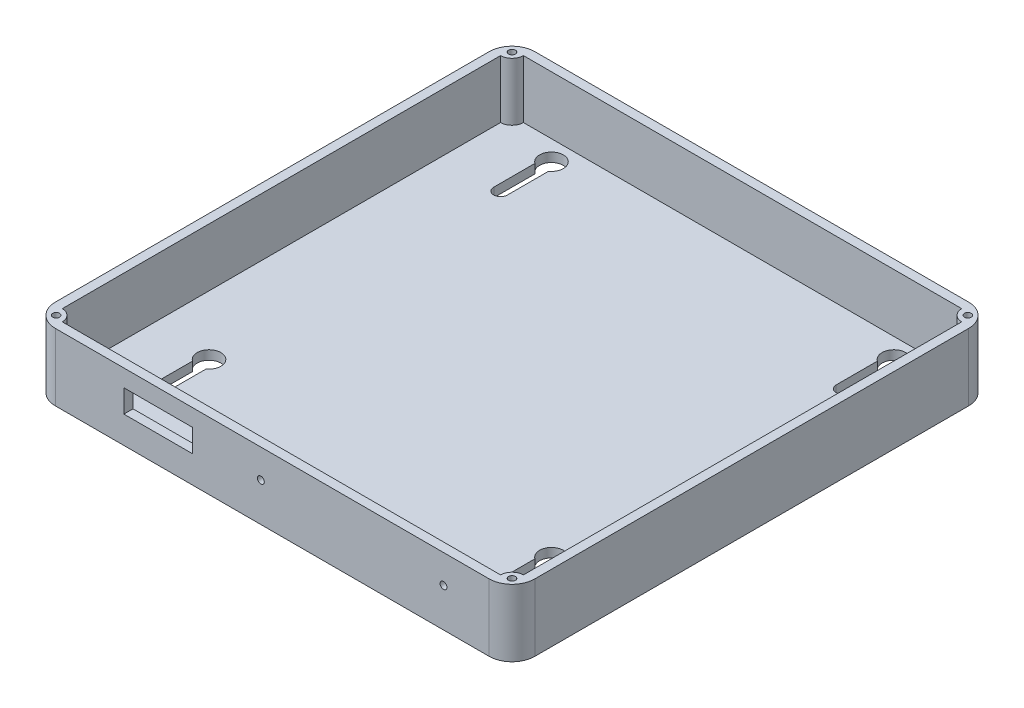
SolidWorks part; units mm, degrees
ref_plane "Front Plane" through (0, 0, 0) normal (0, 0, 1) x (1, 0, 0)
ref_plane "Top Plane" through (0, 0, 0) normal (0, 1, 0) x (1, 0, 0)
ref_plane "Right Plane" through (0, 0, 0) normal (1, 0, 0) x (0, 0, -1)
sketch "Sketch1" plane through (0, 0, 0) normal (0, 1, 0) x (1, 0, 0)
  line L0 (-101, -101) -> (-101, 101)
  line L1 (-105, -105) -> (105, -105)
  line L2 (-105, -105) -> (-105, 105)
  line L3 (-105, 105) -> (105, 105)
  line L4 (105, -105) -> (105, 105)
  line L5 (-101, 101) -> (101, 101)
  line L6 (101, -101) -> (101, 101)
  line L7 (-101, -101) -> (101, -101)
  point P0 (0, 0)
  point P6 (0, 105)
  point P7 (-105, 0)
  dimension "D1" = 210
  dimension "D2" = 210
  dimension "D3" = 4
extrude "Base" add sketch "Sketch1" along normal blind 4 contours L1 L4 L3 L2
extrude "Walls" add sketch "Sketch1<3>" along normal blind 25.4 from surface starting at face at (0, 4, 0)
sketch "Sketch1<3>" plane through (0, 0, 0) normal (0, 1, 0) x (1, 0, 0) same geometry as "Sketch1"
sketch "Sketch2" plane through (0, 29.4, 0) normal (0, 1, 0) x (1, 0, 0)
  line L0 (-101, 101) -> (-101, 96)
  line L1 (-101, 101) -> (-101, -101) construction
  line L2 (-101, 101) -> (-96, 101)
  line L3 (101, 101) -> (-101, 101) construction
  line L12 (-101, 101) -> (-97.4645, 97.4645) construction
  line L27 (-16.72, 0) -> (16.72, 0) construction
  line L28 (-101, -101) -> (-101, -96)
  line L29 (-101, -101) -> (-96, -101)
  line L30 (0, -16.72) -> (0, 16.72) construction
  line L31 (101, 101) -> (101, 96)
  line L32 (101, 101) -> (96, 101)
  line L33 (101, -101) -> (96, -101)
  line L34 (101, -101) -> (101, -96)
  arc A0 (-101, 96) -> (-96, 101) centre (-101, 101) ccw
  circle A18 centre (-99.8333, 99.8333) radius 1.5
  arc A19 (-101, -96) -> (-96, -101) centre (-101, -101) cw
  circle A20 centre (-99.8333, -99.8333) radius 1.5
  arc A21 (101, 96) -> (96, 101) centre (101, 101) cw
  circle A22 centre (99.8333, 99.8333) radius 1.5
  circle A23 centre (99.8333, -99.8333) radius 1.5
  arc A24 (101, -96) -> (96, -101) centre (101, -101) ccw
  dimension "D2" = 1.65
  dimension "D3" = 3
  dimension "D1" = 5
extrude "ScrewMounts" add sketch "Sketch2" against normal up to surface (25.4 mm away) contours A0 L2 L0 | A20 | L28 A19 L29 | L33 A24 L34 | L31 A21 L32 up to face at (0, 4, 0)
extrude "ScrewHoles" cut sketch "Sketch2<5>" against normal blind 12.5 contours A23 | A18 | A20 | A22
sketch "Sketch2<5>" plane through (0, 29.4, 0) normal (0, 1, 0) x (1, 0, 0) same geometry as "Sketch2"
fillet "RoundedCorners" radius 10 4 edges at (-105, 14.7, -105) (105, 14.7, -105) (105, 14.7, 105) (-105, 14.7, 105)
sketch "Sketch3" plane through (0, 0, 0) normal (0, -1, 0) x (1, 0, 0)
  line L0 (-77.985, 80) -> (-77.985, 61.974)
  line L1 (-72.015, 80) -> (-72.015, 61.974)
  line L2 (-105, 95) -> (-105, -95) construction
  line L3 (-95, 105) -> (95, 105) construction
  line L4 (0, -16.72) -> (0, 16.72) construction
  line L5 (77.985, 80) -> (77.985, 61.974)
  line L6 (72.015, 80) -> (72.015, 61.974)
  line L7 (-75, 57.71) -> (75, 57.71) construction
  line L8 (-75, 57.71) -> (-75, -92.29) construction
  line L9 (72.015, -70) -> (72.015, -88.026)
  line L10 (-77.985, -70) -> (-77.985, -88.026)
  line L11 (-72.015, -70) -> (-72.015, -88.026)
  line L12 (77.985, -70) -> (77.985, -88.026)
  arc A0 (-77.985, 61.974) -> (-72.015, 61.974) centre (-75, 57.71) ccw
  arc A1 (-72.015, 80) -> (-77.985, 80) centre (-75, 80) ccw
  arc A2 (72.015, 80) -> (77.985, 80) centre (75, 80) cw
  arc A3 (77.985, 61.974) -> (72.015, 61.974) centre (75, 57.71) cw
  arc A6 (-77.985, -88.026) -> (-72.015, -88.026) centre (-75, -92.29) ccw
  arc A7 (-77.985, -70) -> (-72.015, -70) centre (-75, -70) cw
  arc A8 (77.985, -70) -> (72.015, -70) centre (75, -70) ccw
  arc A9 (77.985, -88.026) -> (72.015, -88.026) centre (75, -92.29) cw
  dimension "D2" = 10.41
  dimension "D3" = 5.97
  dimension "D7" = 150
  dimension "D1" = 22.29
  dimension "D4" = 30
  dimension "D5" = 25
  dimension "D6" = 150
extrude "BackHoleMounts" cut sketch "Sketch3" against normal up to surface (4 mm away) up to face at (0, 4, 0)
sketch "Sketch4" plane through (0, 0, 105) normal (0, 0, 1) x (1, 0, 0)
  line L0 (-95, 0) -> (95, 0) construction
  line L1 (95, 0) -> (95, 29.4) construction
  line L3 (-65, 11.9) -> (-35, 11.9)
  line L4 (-65, 11.9) -> (-65, 21.9)
  line L5 (-65, 21.9) -> (-35, 21.9)
  line L6 (-35, 11.9) -> (-35, 21.9)
  circle A0 centre (75, 16.9) radius 1.5
  circle A1 centre (-5, 16.9) radius 1.5
  point P6 (-35, 16.9)
  dimension "D2" = 3
  dimension "D1" = 16.9
  dimension "D3" = 80
  dimension "D4" = 20
  dimension "D5" = 30
  dimension "D6" = 10
  dimension "D7" = 30
extrude "BatteryPack" cut sketch "Sketch4" against normal up to surface (4 mm away) up to face at (0, 16.7, 101)
